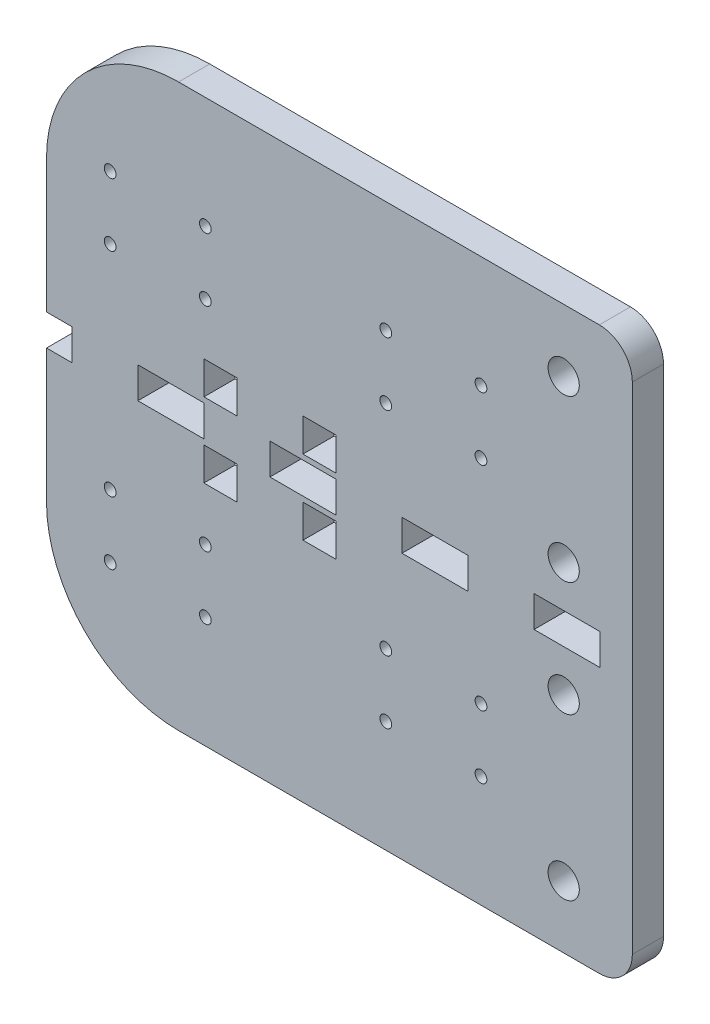
SolidWorks part; units mm, degrees
ref_plane "Front Plane" through (0, 0, 0) normal (0, 0, 1) x (1, 0, 0)
ref_plane "Top Plane" through (0, 0, 0) normal (0, 1, 0) x (1, 0, 0)
ref_plane "Right Plane" through (0, 0, 0) normal (1, 0, 0) x (0, 0, -1)
sketch "Sketch1" plane through (0, 0, 0) normal (0, 0, 1) x (-1, 0, 0)
  line L0 (5.4449, 19.1182) -> (-12.8627, 19.1182) construction
  line L1 (-15.4204, 35.8131) -> (8.0026, 35.8131) construction
  line L2 (-15.4204, 35.8131) -> (-15.4204, 14.5439) construction
  line L3 (-15.4204, 14.5439) -> (8.0026, 14.5439) construction
  line L4 (8.0026, 35.8131) -> (8.0026, 14.5439) construction
  line L5 (5.4449, 19.1182) -> (5.4449, 31.2335) construction
  line L6 (5.4449, 31.2335) -> (-12.8627, 31.2335) construction
  line L7 (-12.8627, 31.2335) -> (-12.8627, 19.1182) construction
  line L8 (-15.4204, 14.5439) -> (-15.4204, -17.2061) construction
  line L9 (-35.7704, 4.6785) -> (-35.7704, 45.6785) construction
  line L10 (-35.7704, 45.6785) -> (-21.7704, 45.6785) construction
  line L11 (-21.7704, 45.6785) -> (-21.7704, 4.6785) construction
  line L12 (-21.7704, 4.6785) -> (-35.7704, 4.6785) construction
  line L13 (-1015.4204, -1.3311) -> (48984.5796, -1.3311) construction
  line L14 (-35.7704, 1.6661) -> (-23.0704, 1.6661)
  line L15 (-21.7704, -7.3406) -> (-35.7704, -7.3406) construction
  line L16 (-21.7704, -48.3406) -> (-21.7704, -7.3406) construction
  line L17 (-35.7704, -48.3406) -> (-21.7704, -48.3406) construction
  line L18 (-35.7704, -7.3406) -> (-35.7704, -48.3406) construction
  line L19 (-12.8627, -33.8956) -> (-12.8627, -21.7803) construction
  line L20 (5.4449, -33.8956) -> (-12.8627, -33.8956) construction
  line L21 (5.4449, -21.7803) -> (5.4449, -33.8956) construction
  line L22 (8.0026, -38.4752) -> (8.0026, -17.2061) construction
  line L23 (-15.4204, -17.2061) -> (8.0026, -17.2061) construction
  line L24 (-15.4204, -38.4752) -> (-15.4204, -17.2061) construction
  line L25 (-15.4204, -38.4752) -> (8.0026, -38.4752) construction
  line L26 (5.4449, -21.7803) -> (-12.8627, -21.7803) construction
  line L27 (-15.4204, -27.8406) -> (-21.7704, -27.8406)
  line L28 (-15.4204, -1.3311) -> (-15.4204, 8.6689) construction
  line L29 (-10.3704, 1.6661) -> (2.3296, 1.6661)
  line L30 (19.9026, 52.6921) -> (45.3026, 52.6921)
  line L31 (15.0296, 1.6661) -> (27.7296, 1.6661)
  line L32 (-964.4397, 2.6689) -> (49035.5603, 2.6689) construction
  line L33 (-964.4397, -5.3311) -> (49035.5603, -5.3311) construction
  line L34 (40.4296, 1.6661) -> (53.1296, 1.6661)
  line L35 (65.8296, 1.6661) -> (70.7026, 1.6661)
  line L36 (15.0296, 2.6689) -> (15.0296, 9.0189)
  line L37 (15.0296, 9.0189) -> (21.3796, 9.0189)
  line L38 (15.0296, 2.6689) -> (21.3796, 2.6689)
  line L39 (19.9026, 52.6921) -> (-35.6234, 52.6921)
  line L40 (40.4296, -5.3311) -> (40.4296, -11.6811)
  line L41 (34.0796, -5.3311) -> (40.4296, -5.3311)
  line L42 (34.0796, -11.6811) -> (40.4296, -11.6811)
  line L43 (34.0796, -5.3311) -> (34.0796, -11.6811)
  line L44 (-35.7704, -4.3283) -> (-35.7704, 1.6661)
  line L45 (21.3796, 2.6689) -> (21.3796, 9.0189)
  line L46 (-23.0704, 1.6661) -> (-23.0704, -4.3283)
  line L47 (21.3796, -5.3311) -> (21.3796, -11.6811)
  line L48 (-10.3704, -4.3283) -> (-10.3704, 1.6661)
  line L49 (34.0796, 2.6689) -> (34.0796, 9.0189)
  line L50 (34.0796, 9.0189) -> (40.4296, 9.0189)
  line L51 (19.9026, -55.3542) -> (-35.6234, -55.3542)
  line L52 (-41.9734, 46.3421) -> (-41.9734, -49.0042)
  line L53 (34.0796, 2.6689) -> (40.4296, 2.6689)
  line L54 (2.3296, 1.6661) -> (2.3296, -4.3283)
  line L55 (15.0296, -5.3311) -> (21.3796, -5.3311)
  line L56 (15.0296, -4.3283) -> (15.0296, 1.6661)
  line L57 (40.4296, 2.6689) -> (40.4296, 9.0189)
  line L58 (27.7296, 1.6661) -> (27.7296, -4.3283)
  line L59 (15.0296, -11.6811) -> (21.3796, -11.6811)
  line L60 (40.4296, -4.3283) -> (40.4296, 1.6661)
  line L61 (70.7026, 27.2921) -> (70.7026, 1.6661)
  line L62 (53.1296, 1.6661) -> (53.1296, -4.3283)
  line L63 (15.0296, -5.3311) -> (15.0296, -11.6811)
  line L64 (65.8296, -4.3283) -> (65.8296, 1.6661)
  line L65 (-15.4204, 25.1785) -> (-21.7704, 25.1785)
  line L66 (65.8296, -4.3283) -> (70.7026, -4.3283)
  line L67 (40.4296, -4.3283) -> (53.1296, -4.3283)
  line L68 (15.0296, -4.3283) -> (27.7296, -4.3283)
  line L69 (-10.3704, -4.3283) -> (2.3296, -4.3283)
  line L70 (-35.7704, -4.3283) -> (-23.0704, -4.3283)
  line L71 (19.9026, -55.3542) -> (45.3026, -55.3542)
  line L72 (70.7026, -29.9542) -> (70.7026, -4.3283)
  line L73 (58.4641, 19.1182) -> (40.1564, 19.1182) construction
  line L75 (37.5987, 35.8131) -> (61.0218, 35.8131) construction
  line L76 (37.5987, 35.8131) -> (37.5987, 14.5439) construction
  line L77 (37.5987, 14.5439) -> (61.0218, 14.5439) construction
  line L78 (61.0218, 35.8131) -> (61.0218, 14.5439) construction
  line L79 (58.4641, 19.1182) -> (58.4641, 31.2335) construction
  line L80 (58.4641, 31.2335) -> (40.1564, 31.2335) construction
  line L81 (40.1564, 31.2335) -> (40.1564, 19.1182) construction
  line L82 (58.4641, -33.901) -> (40.1564, -33.901) construction
  line L83 (37.5987, -17.2061) -> (61.0218, -17.2061) construction
  line L84 (37.5987, -17.2061) -> (37.5987, -38.4752) construction
  line L85 (37.5987, -38.4752) -> (61.0218, -38.4752) construction
  line L86 (61.0218, -17.2061) -> (61.0218, -38.4752) construction
  line L87 (58.4641, -33.901) -> (58.4641, -21.7857) construction
  line L88 (58.4641, -21.7857) -> (40.1564, -21.7857) construction
  line L89 (40.1564, -21.7857) -> (40.1564, -33.901) construction
  arc A0 (-35.6234, 52.6921) -> (-41.9734, 46.3421) centre (-35.6234, 46.3421) ccw
  circle A1 centre (40.1564, 31.2335) radius 1.1321
  circle A2 centre (-12.8627, 31.2335) radius 1.1321
  circle A3 centre (5.4449, 31.2335) radius 1.1321
  circle A4 centre (-28.7704, -43.3406) radius 3
  circle A5 centre (-28.7704, -12.3406) radius 3
  circle A6 centre (-12.8627, -21.7803) radius 1.1321
  circle A7 centre (5.4449, -21.7803) radius 1.1321
  circle A8 centre (5.4449, 19.1182) radius 1.1321
  circle A9 centre (-12.8627, 19.1182) radius 1.1321
  circle A10 centre (5.4449, -33.8956) radius 1.1321
  circle A11 centre (-12.8627, -33.8956) radius 1.1321
  circle A12 centre (-28.7704, 9.6785) radius 3
  circle A13 centre (58.4641, 31.2335) radius 1.1321
  circle A14 centre (-28.7704, 40.6785) radius 3
  circle A15 centre (58.4641, 19.1182) radius 1.1321
  circle A16 centre (40.1564, 19.1182) radius 1.1321
  circle A17 centre (40.1564, -21.7857) radius 1.1321
  circle A18 centre (58.4641, -21.7857) radius 1.1321
  arc A19 (-35.6234, -55.3542) -> (-41.9734, -49.0042) centre (-35.6234, -49.0042) cw
  circle A20 centre (58.4641, -33.901) radius 1.1321
  circle A21 centre (40.1564, -33.901) radius 1.1321
  arc A22 (45.3026, -55.3542) -> (70.7026, -29.9542) centre (45.3026, -29.9542) ccw
  arc A23 (45.3026, 52.6921) -> (70.7026, 27.2921) centre (45.3026, 27.2921) cw
  point P42 (-15.4204, -1.3311)
  dimension "D11" = 6.35
  dimension "D2" = 25.4
  dimension "D3" = 25.4
  dimension "D5" = 31.75
  dimension "D12" = 4
extrude "Boss-Extrude1" add sketch "Sketch1" along normal blind 5.9944 contours A19 L51 L57 L52 A10 A6 A4 A5 A7 A11 region at (-13.406, 1.3311, 0)
